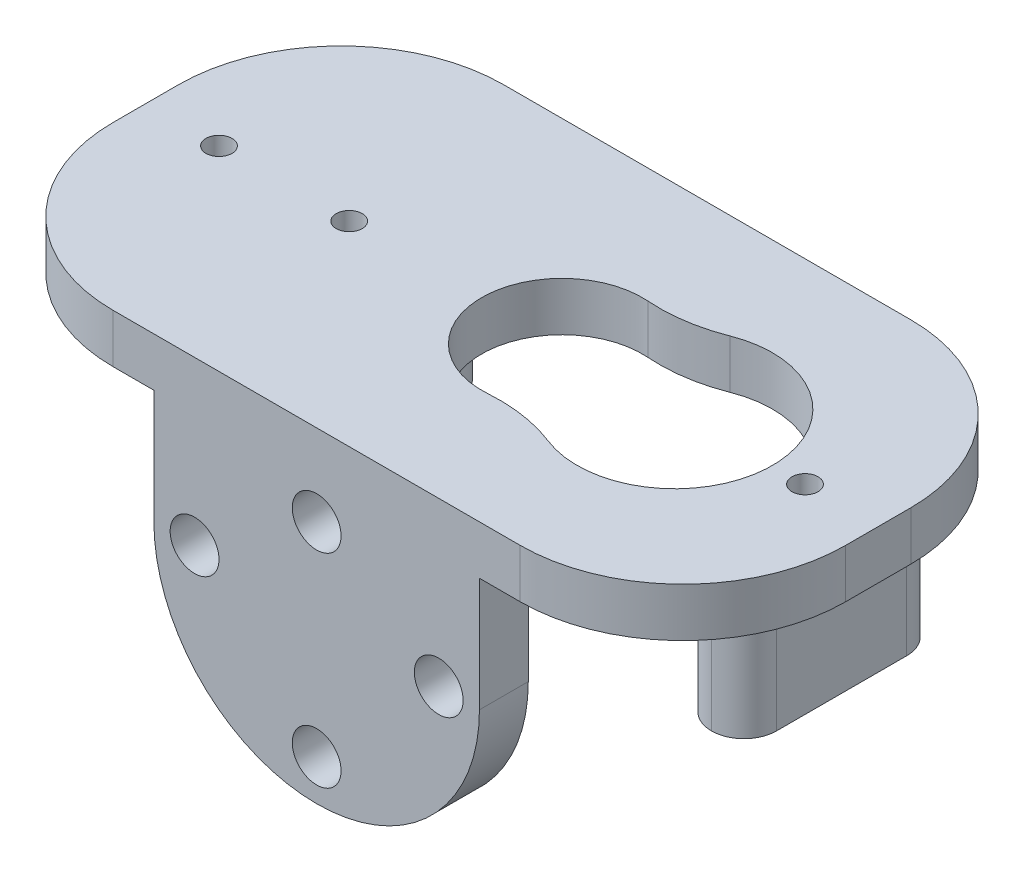
SolidWorks part; units mm, degrees
ref_plane "Front Plane" through (0, 0, 0) normal (0, 0, 1) x (1, 0, 0)
ref_plane "Top Plane" through (0, 0, 0) normal (0, 1, 0) x (1, 0, 0)
ref_plane "Right Plane" through (0, 0, 0) normal (1, 0, 0) x (0, 0, -1)
sketch "Sketch1" plane through (0, 0, 0) normal (0, 1, 0) x (1, 0, 0)
  line L1 (22.5, -12) -> (-22.5, -12)
  line L2 (22.5, -12) -> (22.5, 12)
  line L3 (22.5, 12) -> (-22.5, 12)
  line L4 (-22.5, -12) -> (-22.5, 12)
  line L5 (22.5, -12) -> (-22.5, 12) construction
  line L6 (22.5, 12) -> (-22.5, -12) construction
  point P0 (0, 0)
  dimension "D1" = 24
  dimension "D2" = 45
extrude "Boss-Extrude1" add sketch "Sketch1" along normal blind 3
sketch "Sketch2" plane through (0, 3, 0) normal (0, 1, 0) x (1, 0, 0)
  arc A0 (7.8096, -5.5859) -> (7.8096, 5.5859) centre (10, 0) ccw
  circle A1 centre (18, 0) radius 0.8
  circle A2 centre (-10, 0) radius 0.8
  circle A3 centre (-18, 0) radius 0.8
  arc A4 (3.4303, 4.9223) -> (3.4303, -4.9223) centre (3.0706, 0) ccw
  arc A5 (7.8096, -5.5859) -> (3.4303, -4.9223) centre (4.1589, -14.8957) ccw
  arc A6 (7.8096, 5.5859) -> (3.4303, 4.9223) centre (4.1589, 14.8957) cw
  dimension "D1" = 12
  dimension "D3" = 1.6
  dimension "D4" = 8
  dimension "D5" = 1.6
  dimension "D6" = 20
  dimension "D7" = 1.6
  dimension "D8" = 8
  dimension "D9" = 10
  dimension "D2" = 10
extrude "Cut-Extrude1" cut sketch "Sketch2" against normal through all
sketch "Sketch3" plane through (0, 0, 0) normal (0, -1, 0) x (1, 0, 0)
  line L1 (-11.25, 6) -> (-7.25, 6)
  line L2 (-11.25, 6) -> (-11.25, -6)
  line L3 (-11.25, -6) -> (-7.25, -6)
  line L4 (-7.25, 6) -> (-7.25, -6)
  line L5 (16.25, 6) -> (20.25, 6)
  line L6 (16.25, 6) -> (16.25, -6)
  line L7 (16.25, -6) -> (20.25, -6)
  line L8 (20.25, 6) -> (20.25, -6)
  circle A0 centre (10, 0) radius 6 construction
  point P4 (-7.25, 0)
  point P12 (18.25, 6)
  dimension "D4" = 8.25
  dimension "D1" = 4
  dimension "D2" = 12
  dimension "D3" = 4
  dimension "D5" = 27.5
extrude "Boss-Extrude2" add sketch "Sketch3" along normal blind 7
sketch "Sketch4" plane through (0, -7, 0) normal (0, -1, 0) x (1, 0, 0)
  circle A0 centre (18.25, 0) radius 0.8
  circle A1 centre (-9.25, 0) radius 0.8
  dimension "D1" = 1.6
  dimension "D2" = 1.6
extrude "Cut-Extrude2" cut sketch "Sketch4" against normal blind 5
fillet "Fillet1" radius 2 8 edges at (16.25, -3.5, -6) (-11.25, -3.5, -6) (-7.25, -3.5, -6) (20.25, -3.5, -6) (-11.25, -3.5, 6) (-7.25, -3.5, 6) (16.25, -3.5, 6) (20.25, -3.5, 6)
fillet "Fillet2" radius 10 4 edges at (-22.5, 1.5, -12) (22.5, 1.5, -12) (-22.5, 1.5, 12) (22.5, 1.5, 12)
sketch "Sketch6" plane through (0, 0, 0) normal (0, -1, 0) x (1, 0, 0)
  line L0 (-12.5, 12) -> (12.5, 12) construction
  line L1 (-10, 12) -> (10, 12)
  line L2 (-10, 12) -> (-10, 9)
  line L3 (-10, 9) -> (10, 9)
  line L4 (10, 12) -> (10, 9)
  line L5 (12.5, -12) -> (-12.5, -12) construction
  point P6 (0, 9)
  point P9 (0, -12)
  dimension "D1" = 3
  dimension "D2" = 20
extrude "Boss-Extrude3" add sketch "Sketch6" along normal blind 17
fillet "Fillet3" radius 10 2 edges at (-10, -17, 10.5) (10, -17, 10.5)
sketch "Sketch7" plane through (0, 0, 12) normal (0, 0, 1) x (1, 0, 0)
  circle A0 centre (0, -14.5) radius 1.5
  circle A1 centre (0, -2) radius 1.5
  arc A2 (-10, -7) -> (0, -17) centre (0, -7) ccw construction
  arc A3 (0, -17) -> (10, -7) centre (0, -7) ccw construction
  circle A4 centre (7.5, -7) radius 1.5
  circle A5 centre (-7.5, -7) radius 1.5
  dimension "D1" = 3
  dimension "D2" = 3
  dimension "D3" = 5
  dimension "D4" = 7.5
  dimension "D5" = 3
  dimension "D6" = 3
  dimension "D7" = 7.5
  dimension "D8" = 7.5
extrude "Cut-Extrude3" cut sketch "Sketch7" against normal blind 3
